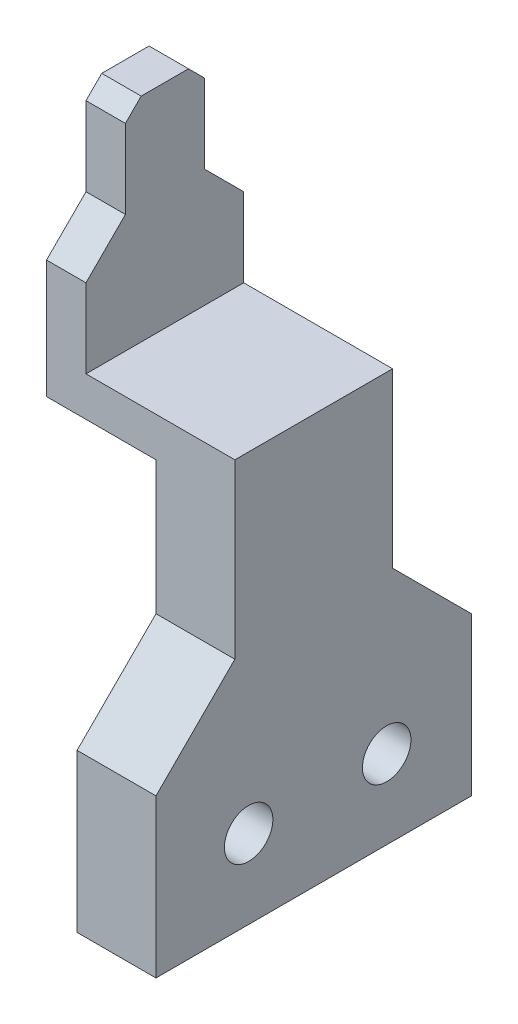
SolidWorks part; units mm, degrees
ref_plane "前视基准面" through (0, 0, 0) normal (0, 0, 1) x (1, 0, 0)
ref_plane "上视基准面" through (0, 0, 0) normal (0, 1, 0) x (1, 0, 0)
ref_plane "右视基准面" through (0, 0, 0) normal (1, 0, 0) x (0, 0, -1)
sketch "草图1" plane through (0, 0, 0) normal (1, 0, 0) x (0, 0, -1)
  line L1 (0, 0) -> (40, 0)
  line L2 (0, 0) -> (0, 20)
  line L3 (0, 20) -> (40, 20)
  line L4 (40, 0) -> (40, 20)
  dimension "D1" = 20
  dimension "D2" = 40
extrude "凸台-拉伸1" add sketch "草图1" along normal blind 10
sketch "草图2" plane through (10, 0, 0) normal (1, 0, 0) x (0, 0, -1)
  circle A0 centre (11.75, 10) radius 3.0738
  circle A1 centre (29.25, 10) radius 3.0738
extrude "切除-拉伸1" cut sketch "草图2" against normal blind 10
sketch "草图3" plane through (0, 0, -40) normal (0, 0, -1) x (-1, 0, 0)
  line L0 (0, 20) -> (0, 46.899)
  line L1 (23.875, 46.899) -> (37.75, 46.899) construction
  line L2 (0, 46.899) -> (13.875, 46.899)
  line L3 (13.875, 46.899) -> (13.875, 78.899)
  line L4 (13.875, 78.899) -> (8.875, 78.899)
  line L5 (8.875, 61.899) -> (8.875, 81.899) construction
  line L6 (8.875, 78.899) -> (8.875, 51.899)
  line L7 (8.875, 51.899) -> (-10, 51.899)
  line L8 (-10, 51.899) -> (-10, 20)
  line L9 (-10, 20) -> (0, 20)
  line L10 (8.875, 81.899) -> (28.875, 81.899) construction
  dimension "D1" = 5
  dimension "D2" = 5
  dimension "D3" = 3
extrude "凸台-拉伸2" add sketch "草图3" against normal up to surface (40 mm away) up to face at (5, 10, 0)
sketch "草图4" plane through (10, 0, 0) normal (1, 0, 0) x (0, 0, -1)
  line L0 (30, 30) -> (30, 88.4482)
  line L1 (30, 88.4482) -> (51.1955, 88.4482)
  line L2 (51.1955, 88.4482) -> (51.1955, 8.8045)
  line L3 (30, 30) -> (51.1955, 8.8045)
  line L4 (10, 30) -> (10, 90.8014)
  line L5 (10, 90.8014) -> (0, 90.8014)
  line L6 (0, 90.8014) -> (0, 20)
  line L7 (0, 46.899) -> (0, 0) construction
  line L8 (0, 20) -> (10, 30) construction
  line L9 (0, 20) -> (10, 30)
extrude "切除-拉伸2" cut sketch "草图4" against normal through all
sketch "草图5" plane through (-8.875, 0, 0) normal (1, 0, 0) x (0, 0, -1)
  line L0 (10, 61.899) -> (15, 61.899)
  line L1 (10, 51.899) -> (10, 78.899) construction
  line L2 (-432.9609, 61.899) -> (567.0391, 61.899) construction
  line L3 (15, 61.899) -> (15, 78.899)
  line L4 (10, 78.899) -> (30, 78.899) construction
  line L5 (15, 78.899) -> (10, 78.899)
  line L6 (10, 78.899) -> (10, 61.899)
  line L7 (30, 78.899) -> (25, 78.899)
  line L8 (25, 78.899) -> (25, 61.899)
  line L9 (25, 61.899) -> (30, 61.899)
  line L10 (30, 78.899) -> (30, 51.899) construction
  line L11 (30, 61.899) -> (30, 78.899)
  dimension "D1" = 5
  dimension "D2" = 5
extrude "切除-拉伸3" cut sketch "草图5" against normal through all
chamfer "倒角1" distance 5 angle 45 2 edges at (-11.375, 61.899, -25) (-11.375, 61.899, -15)
chamfer "倒角2" distance 2 angle 45 2 edges at (-11.375, 78.899, -15) (-11.375, 78.899, -25)
